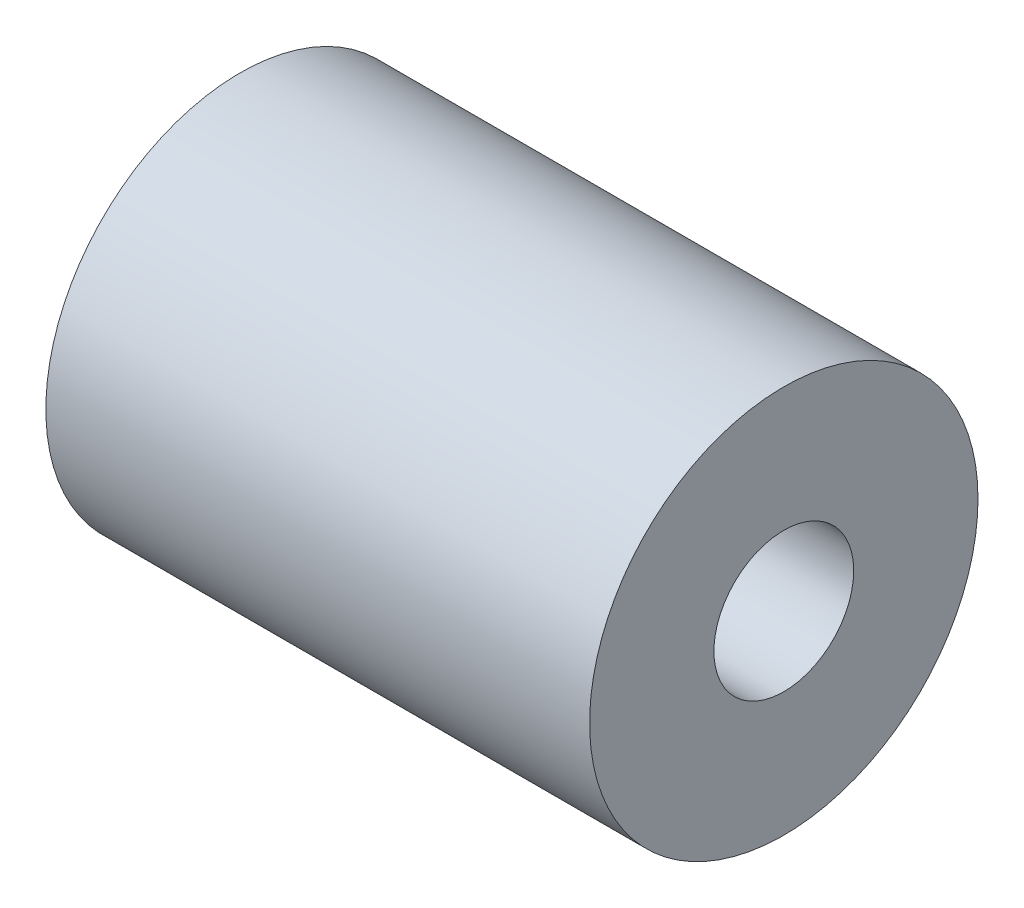
SolidWorks part; units mm, degrees
ref_plane "Front Plane" through (0, 0, 0) normal (0, 0, 1) x (1, 0, 0)
ref_plane "Top Plane" through (0, 0, 0) normal (0, 1, 0) x (1, 0, 0)
ref_plane "Right Plane" through (0, 0, 0) normal (1, 0, 0) x (0, 0, -1)
sketch "Sketch1" plane through (0, 0, 0) normal (1, 0, 0) x (0, 0, -1)
  circle A0 centre (0, 0) radius 1.8
  circle A1 centre (0, 0) radius 5
  dimension "D1" = 3.6
  dimension "D2" = 10
extrude "Boss-Extrude1" add sketch "Sketch1" along normal blind 14
